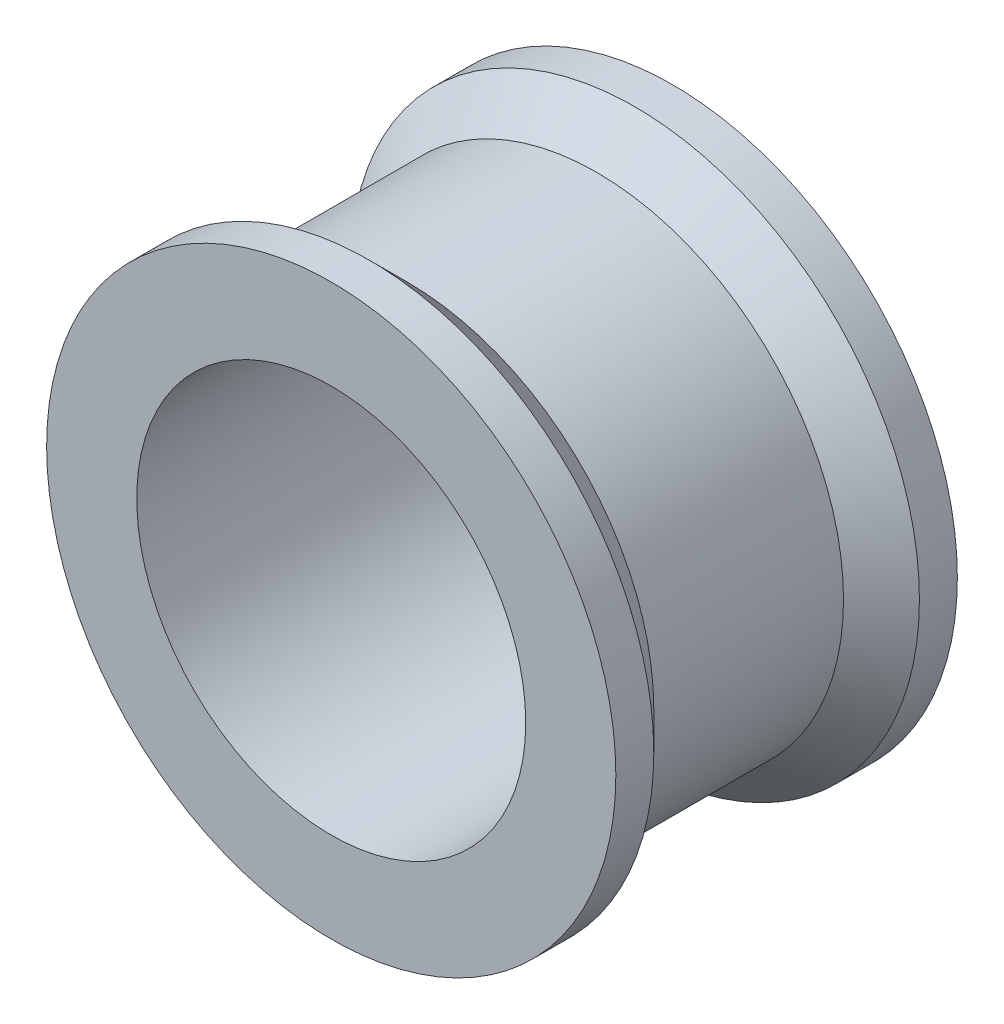
SolidWorks part; units mm, degrees
ref_plane "Front Plane" through (0, 0, 0) normal (0, 0, 1) x (1, 0, 0)
ref_plane "Top Plane" through (0, 0, 0) normal (0, 1, 0) x (1, 0, 0)
ref_plane "Right Plane" through (0, 0, 0) normal (1, 0, 0) x (0, 0, -1)
sketch "Sketch1" plane through (0, 0, 0) normal (0, 0, 1) x (1, 0, 0)
  circle A0 centre (0, 0) radius 5.125
  circle A1 centre (0, 0) radius 7.5
  dimension "D1" = 10.25
  dimension "D2" = 15
extrude "Boss-Extrude1" add sketch "Sketch1" along normal blind 1
sketch "Sketch2" plane through (0, 0, 1) normal (0, 0, 1) x (1, 0, 0)
  circle A0 centre (0, 0) radius 5.125
  circle A1 centre (0, 0) radius 6.5
  circle A2 centre (0, 0) radius 5.125 construction
  dimension "D1" = 13
extrude "Boss-Extrude2" add sketch "Sketch2" along normal blind 3.5
chamfer "Chamfer1" distance 1 angle 45 1 edges at (6.5, 0, 1)
mirror "Mirror5" about plane through (0, 0, 4.5) normal (0, 0, 1) of bodies 102
